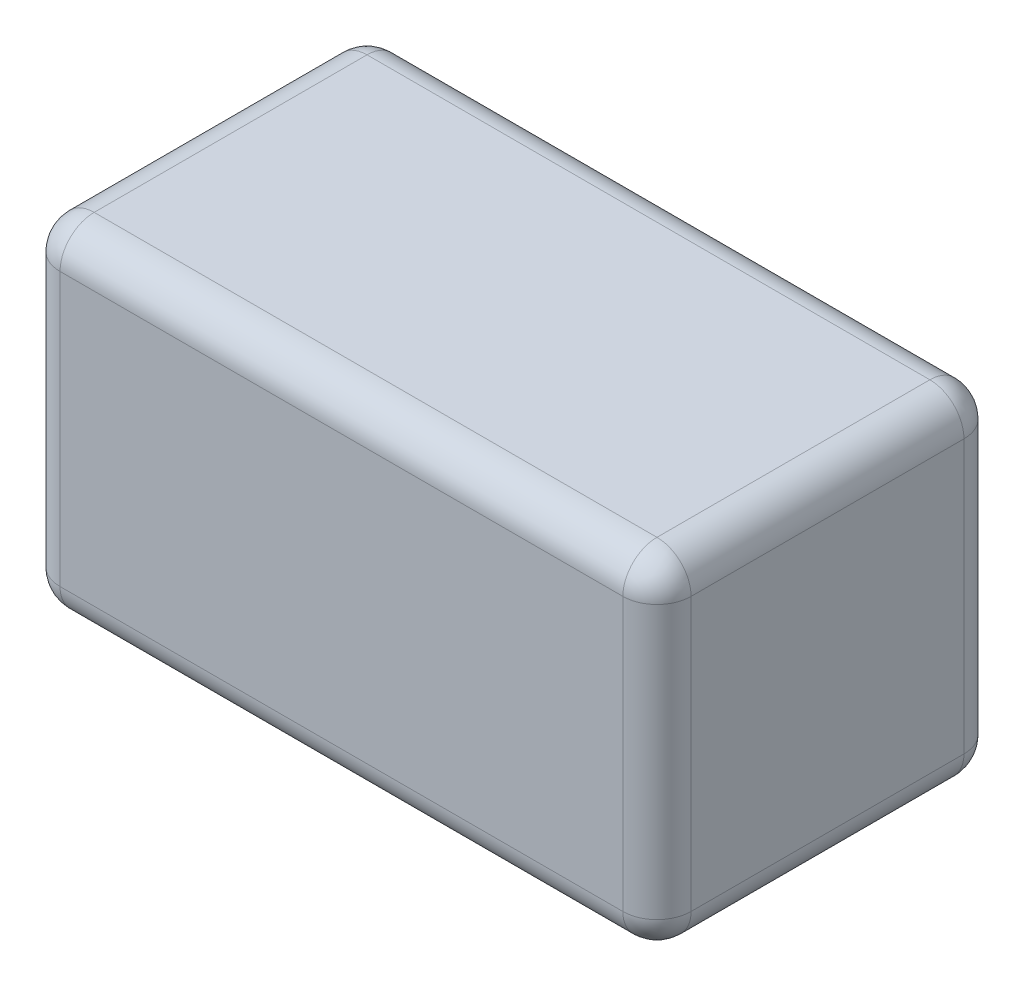
SolidWorks part; units mm, degrees
ref_plane "前视基准面" through (0, 0, 0) normal (0, 0, 1) x (1, 0, 0)
ref_plane "上视基准面" through (0, 0, 0) normal (0, 1, 0) x (1, 0, 0)
ref_plane "右视基准面" through (0, 0, 0) normal (1, 0, 0) x (0, 0, -1)
other "Configuration Table"
sketch "草图1" plane through (0, 0, 0) normal (0, 0, 1) x (1, 0, 0)
  line L1 (-37, -20) -> (37, -20)
  line L2 (-37, -20) -> (-37, 20)
  line L3 (-37, 20) -> (37, 20)
  line L4 (37, -20) -> (37, 20)
  line L5 (-37, -20) -> (37, 20) construction
  line L6 (-37, 20) -> (37, -20) construction
extrude "凸台-拉伸1" add sketch "草图1" along normal mid plane 40
fillet "圆角1" radius 4 12 edges at (37, 0, -20) (0, 20, -20) (-37, 0, -20) (0, -20, -20) (37, 0, 20) (0, 20, 20) (-37, 0, 20) (0, -20, 20) (37, -20, 0) (-37, -20, 0) (-37, 20, 0) (37, 20, 0) tangent propagation no
